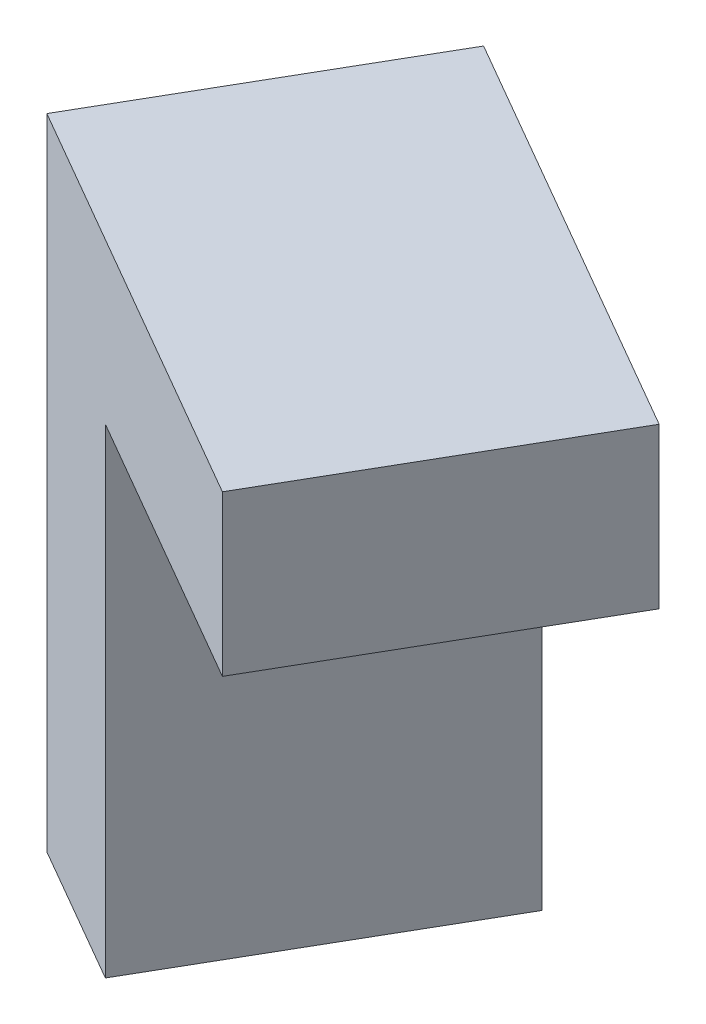
SolidWorks part; units mm, degrees
ref_plane "Front Plane" through (0, 0, 0) normal (0, 0, 1) x (1, 0, 0)
ref_plane "Top Plane" through (0, 0, 0) normal (0, 1, 0) x (1, 0, 0)
ref_plane "Right Plane" through (0, 0, 0) normal (1, 0, 0) x (0, 0, -1)
ref_axis "Axis1" through (0, -4, 0) along (0, -1, 0)
ref_plane "Plane1" through (0, 0, 0) normal (-0.5, 0, 0.866) x (0, -1, 0)
sketch "Sketch1" plane through (0, 0, 0) normal (-0.5, 0, 0.866) x (0, -1, 0)
  line L0 (5, 5) -> (25, 5)
  line L1 (25, 5) -> (25, 10)
  line L2 (25, 10) -> (10, 10)
  line L3 (10, 10) -> (10, 20)
  line L4 (10, 20) -> (5, 20)
  line L5 (5, 20) -> (5, 5)
extrude "Boss-Extrude1" add sketch "Sketch1" along normal blind 10
